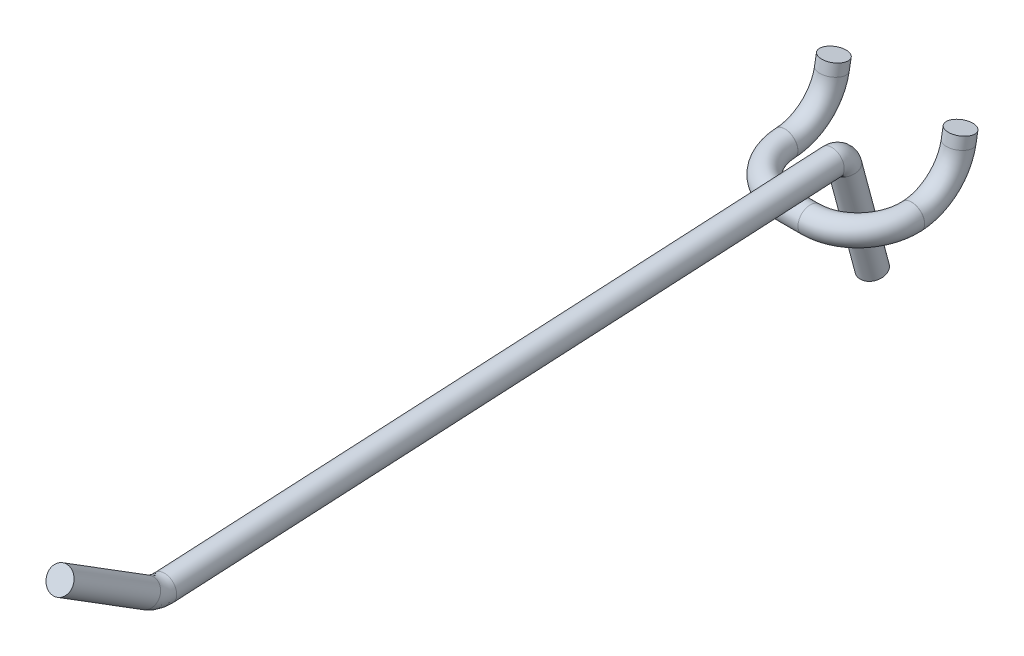
SolidWorks part; units mm, degrees
note: '?' marks a value the reader was unsure of.
ref_plane "Front" through (0, 0, 0) normal (0, 0, 1) x (1, 0, 0)
ref_plane "Top" through (0, 0, 0) normal (0, 1, 0) x (1, 0, 0)
ref_plane "Right" through (0, 0, 0) normal (1, 0, 0) x (0, 0, -1)
sketch "Sketch1" plane through (0, 0, 0) normal (1, 0, 0) x (0, 0, -1)
  line L0 (0, 0) -> (-129.6672, -6.7956)
  line L1 (-133.3646, -5.8394) -> (-151.13, 5.2617)
  line L2 (9.5208, -1.5157) -> (15.24, -22.86)
  line L3 (0, 0) -> (-112.0091, 0) construction
  line L4 (0, 0) -> (0, -32.1536) construction
  line L5 (0, 0) -> (18.5081, -4.11) construction
  line L6 (18.5081, -4.11) -> (20.32, 6.1658) construction
  line L7 (17.78, 6.1658) -> (17.78, -22.86) construction
  line L8 (0, 0) -> (6.9344, 0.3634)
  line L9 (0, 2.54) -> (28.988, 2.54) construction
  line L10 (15.24, -25.4) -> (35.1394, -25.4) construction
  line L11 (0, -5.08) -> (18.5081, -4.11) construction
  line L12 (0, -7.62) -> (32.7624, -5.903) construction
  arc A0 (6.9344, 0.3634) -> (9.5208, -1.5157) centre (7.0674, -2.1731) cw
  arc A1 (-129.6672, -6.7956) -> (-133.3646, -5.8394) centre (-129.9996, -0.4543) cw
  circle A2 centre (20.32, 6.1658) radius 2.54 construction
  circle A3 centre (15.24, -22.86) radius 2.54 construction
  circle A4 centre (-151.13, 5.2617) radius 2.54 construction
  circle A5 centre (0, 0) radius 2.54 construction
  circle A6 centre (-131.5895, -6.602) radius 2.54 construction
  circle A7 centre (0, -5.08) radius 2.54 construction
  point P18 (-153.67, 5.2617)
  point P20 (22.86, 6.1658)
  point P22 (-2.54, 0)
  point P33 (20.32, 8.7058)
  dimension "D1" = 6.35
  dimension "D2" = 15
  dimension "D6" = 2.54
  dimension "D3" = 3
  dimension "D4" = 145
  dimension "D5" = 10
  dimension "proj" = 171.45
  dimension "back extension" = 25.4
  dimension "height down" = 27.94
  dimension "end length" = 22.86
  dimension "height up" = 15.24
  dimension "Wire Diameter" = 5.08
sketch "Sketch2" plane through (0, 0, 0) normal (0, 0, 1) x (1, 0, 0)
  circle A0 centre (0, 0) radius 2.54
  dimension "Wire Diameter" = 5.08
sweep "Sweep1" add profiles "Sketch2" path "Sketch1"
sketch "Sketch3" plane through (0, 0, 0) normal (0, 0, 1) x (1, 0, 0)
  circle A1 centre (0, 0) radius 2.54
  circle A2 centre (0, 0) radius 2.54
  dimension "D1" = 0
sketch "Sketch4" plane through (0, 0, 0) normal (1, 0, 0) x (0, 0, -1)
  line L0 (9.5208, -1.5157) -> (15.24, -22.86) construction
  line L1 (0, 0) -> (6.9344, 0.3634) construction
  line L2 (9.5208, -1.5157) -> (15.24, -22.86)
  line L3 (0, 0) -> (6.9344, 0.3634)
  arc A0 (9.5208, -1.5157) -> (6.9344, 0.3634) centre (7.0674, -2.1731) ccw construction
  arc A1 (9.5208, -1.5157) -> (6.9344, 0.3634) centre (7.0674, -2.1731) ccw
sweep "Sweep2" add profiles "Sketch3" path "Sketch4"
ref_plane "Plane1" through (0, -5.0661, -0.2655) normal (0, 0.9986, 0.0523) x (-1, 0, 0)
sketch "Sketch5" plane through (0, -5.0661, -0.2655) normal (0, 0.9986, 0.0523) x (-1, 0, 0)
  line L0 (0, 0) -> (-12.7, 0)
  line L1 (-12.7, 0) -> (-12.7, -18.2676)
  line L2 (0, -18.2676) -> (-12.7, -18.2676) construction
  line L3 (0, 0) -> (0, -26.477) construction
  circle A0 centre (-12.7, -18.2676) radius 2.54 construction
  point P7 (-15.24, -18.2676)
  dimension "D1" = 25.4
  dimension "Wire Diameter" = 5.08
ref_plane "Plane2" through (12.7, 0, 0) normal (1, 0, 0) x (0, 0, -1)
sketch "Sketch6" plane through (12.7, 0, 0) normal (1, 0, 0) x (0, 0, -1)
  line L0 (18.5081, -4.11) -> (20.32, 6.1658) construction
  line L1 (18.5081, -4.11) -> (20.32, 6.1658)
sketch3d "3DSketch1"
  line L0 (0, -5.0661, -0.2655) -> (12.7, -5.0661, -0.2655) construction
  line L1 (12.7, -5.0661, -0.2655) -> (12.7, -4.11, -18.5081) construction
  line L2 (12.7, -4.11, -18.5081) -> (12.7, 6.1658, -20.32) construction
  line L3 (0, -5.0661, -0.2655) -> (2.54, -5.0661, -0.2655)
  line L4 (12.7, -4.5344, -10.4116) -> (12.7, -4.533, -10.4375)
  line L5 (12.7, 3.8488, -19.9114) -> (12.7, 6.1658, -20.32)
  arc A0 (12.7, -4.533, -10.4375) -> (12.7, 3.8488, -19.9114) centre (12.7, 5.6131, -9.9058) ccw
  arc A1 (2.54, -5.0661, -0.2655) -> (12.7, -4.5344, -10.4116) centre (2.54, -4.5344, -10.4116) ccw
  point P6 (12.7, -4.11, -18.5081)
  point P8 (22.86, 5.6131, -9.9058)
  point P11 (12.7, -5.0661, -0.2655)
  point P13 (2.54, 5.6117, -9.8798)
  dimension "radius-back" = 10.16
sketch "Sketch7" plane through (0, 0, 0) normal (1, 0, 0) x (0, 0, -1)
  circle A0 centre (0, -5.08) radius 2.54 construction
  circle A1 centre (0, -5.08) radius 2.54
sweep "Sweep3" add profiles "Sketch7" path "3DSketch1"
mirror "Mirror2" about plane through (0, 0, 0) normal (1, 0, 0) of bodies 111
sketch "Sketch8" plane through (0, 0, 0) normal (1, 0, 0) x (0, 0, -1)
  line L0 (-149.6731, 7.3423) -> (-116.5495, 60.3511) construction
  line L1 (-133.3646, -5.8394) -> (-151.0173, 5.1913) construction
  line L2 (-133.3646, -5.8394) -> (-151.13, 5.2617) construction
  line L3 (12.7555, -23.3881) -> (20.2805, -21.3718) construction
  line L4 (15.2056, -22.7316) -> (12.4957, -12.6183) construction
  line L5 (9.5208, -1.5157) -> (15.24, -22.86) construction
ref_plane "Plane3" through (0, 5.1913, 151.0173) normal (0, -0.5299, -0.848) x (-1, 0, 0)
other "SurfaceCut1"
ref_plane "Plane4" through (0, -22.7316, -15.2056) normal (0, -0.9659, -0.2588) x (1, 0, 0)
other "SurfaceCut2" flip cut yes
ref_axis "Axis1" through (0, -1.5157, -9.5208) along (0, -0.9659, -0.2588)?
ref_plane "Plane5" through (0, 0, 0) normal (1, 0, 0) x (0, -0.9659, -0.2588)
ref_plane "Plane6" through (0, 2.2787, -8.5041) normal (0, -0.2588, 0.9659) x (0, -0.9659, -0.2588)
ref_axis "Axis2" through (0, 0, 0) along (0, -0.0523, 0.9986)?
ref_plane "Plane7" through (0, 0, 0) normal (0, 0.9986, 0.0523) x (0, -0.0523, 0.9986)
